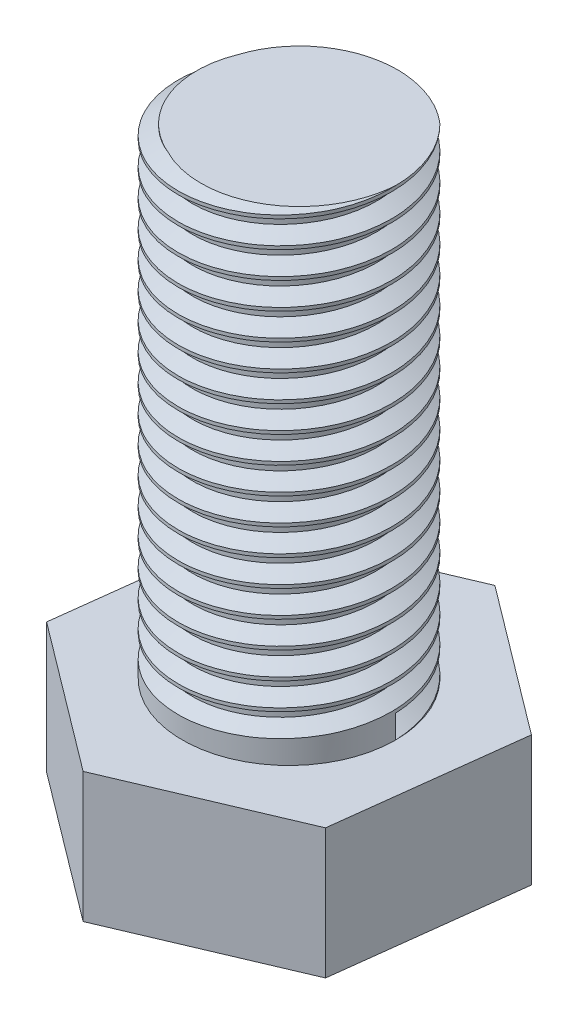
SolidWorks part; units mm, degrees
material "6061 Alloy"
ref_plane "Front Plane" through (0, 0, 0) normal (0, 0, 1) x (1, 0, 0)
ref_plane "Top Plane" through (0, 0, 0) normal (0, 1, 0) x (1, 0, 0)
ref_plane "Right Plane" through (0, 0, 0) normal (1, 0, 0) x (0, 0, -1)
sketch "Sketch2" plane through (0, 0, 0) normal (0, 1, 0) x (1, 0, 0)
  circle A0 centre (0, 0) radius 12.7
  dimension "D1" = 25.4
extrude "Boss-Extrude1" add sketch "Sketch2" along normal blind 57.15
thread "Thread1" pitch 3.175 method cut profile "Thread Profile1" start angle 0, offset 0, length 0, pitch 3.175, diameter 25.4
ref_plane "Plane1" through (12.7, 0, 0) normal (0, 0, 1) x (1, 0, 0)
sketch "Thread Profile1" plane through (12.7, 0, 0) normal (0, 0, 1) x (1, 0, 0)
  line L0 (0, 0) -> (0, 3.175) construction
  line L11 (0, 0) -> (0, 2.7781)
  line L12 (0, 2.7781) -> (-1.7185, 1.7859)
  line L13 (-1.7185, 1.7859) -> (-1.7185, 0.9922)
  line L15 (-1.7185, 0.9922) -> (0, 0)
  line L17 (-1.7185, 1.3891) -> (0, 1.3891) construction
  point P2 (0, 0)
  dimension "Pitch" = 3.175
  dimension "Profile_Angle" = 60
  dimension "Profile_Land" = 0.7937
  dimension "Profile_Height" = 1.7185
sketch "Sketch6" plane through (0, 0, 0) normal (0, -1, 0) x (1, 0, 0)
  line L1 (17.5749, 13.2284) -> (-2.6687, 21.8346)
  line L2 (-2.6687, 21.8346) -> (-20.2436, 8.6061)
  line L3 (-20.2436, 8.6061) -> (-17.5749, -13.2284)
  line L4 (-17.5749, -13.2284) -> (2.6687, -21.8346)
  line L5 (2.6687, -21.8346) -> (20.2436, -8.6061)
  line L6 (20.2436, -8.6061) -> (17.5749, 13.2284)
  circle A0 centre (0, 0) radius 19.05 construction
  dimension "D1" = 38.1
extrude "Boss-Extrude2" add sketch "Sketch6" along normal blind 15.4781
